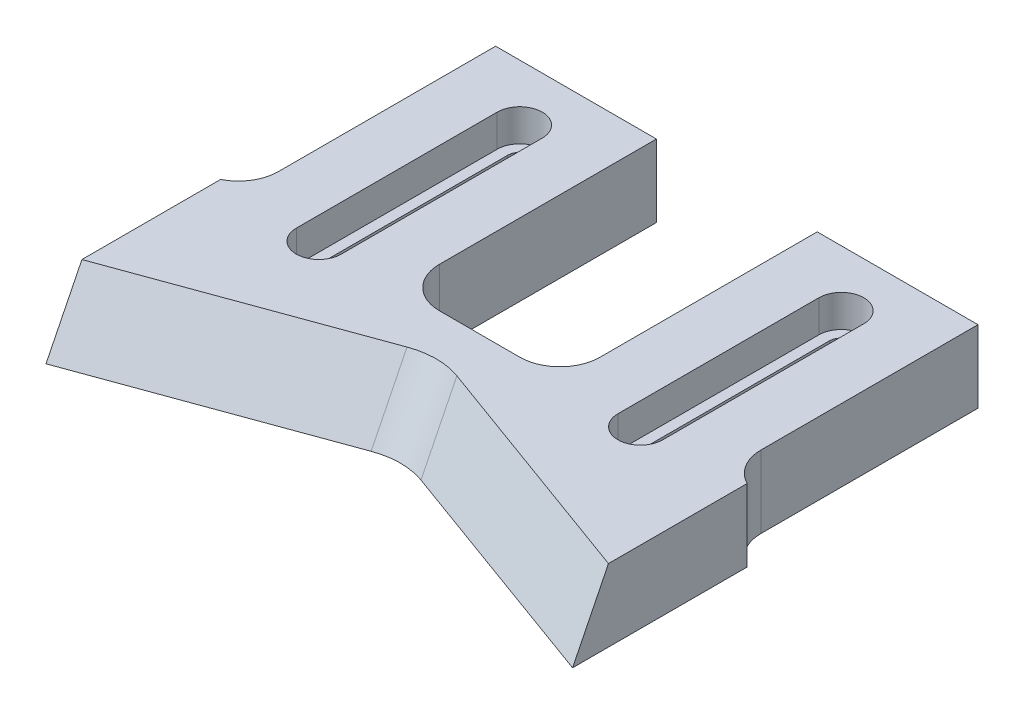
SolidWorks part; units mm, degrees
material "POM Acetal Copolymer"
ref_plane "Front Plane" through (0, 0, 0) normal (0, 0, 1) x (1, 0, 0)
ref_plane "Top Plane" through (0, 0, 0) normal (0, 1, 0) x (1, 0, 0)
ref_plane "Right Plane" through (0, 0, 0) normal (1, 0, 0) x (0, 0, -1)
sketch "Sketch1" plane through (0, 0, 0) normal (0, 1, 0) x (1, 0, 0)
  line L0 (0, 0) -> (0, 55)
  line L1 (0, 55) -> (75.5, 55)
  line L2 (75.5, 55) -> (75.5, 0)
  line L3 (75.5, 0) -> (37.75, 13.7399)
  line L4 (37.75, 13.7399) -> (0, 0)
  dimension "D1" = 55
  dimension "D2" = 70
  dimension "D3" = 75.5
extrude "Boss-Extrude1" add sketch "Sketch1" along normal blind 9
sketch "Sketch4" plane through (0, 9, 0) normal (0, 1, 0) x (1, 0, 0)
  line L0 (17.75, 48) -> (17.75, 23) construction
  line L1 (19.25, 48) -> (19.25, 23)
  line L2 (16.25, 48) -> (16.25, 23)
  line L3 (57.75, 48) -> (57.75, 23) construction
  line L4 (59.25, 48) -> (59.25, 23)
  line L5 (56.25, 48) -> (56.25, 23)
  line L6 (75.5, 55) -> (0, 55) construction
  line L9 (75.5, 55) -> (0, 55) construction
  arc A0 (19.25, 48) -> (16.25, 48) centre (17.75, 48) ccw
  arc A1 (16.25, 23) -> (19.25, 23) centre (17.75, 23) ccw
  arc A2 (59.25, 48) -> (56.25, 48) centre (57.75, 48) ccw
  arc A3 (56.25, 23) -> (59.25, 23) centre (57.75, 23) ccw
  point P2 (17.75, 35.5)
  point P7 (57.75, 35.5)
  point P14 (37.75, 55)
  dimension "D1" = 3
  dimension "D2" = 3
  dimension "D3" = 40
  dimension "D4" = 20
  dimension "D5" = 25
  dimension "D6" = 7
extrude "Cut-Extrude2" cut sketch "Sketch4" against normal up to next
sketch "Sketch5" plane through (0, 9, 0) normal (0, 1, 0) x (1, 0, 0)
  line L0 (75.5, 55) -> (0, 55) construction
  line L1 (27.75, 55) -> (47.75, 55)
  line L2 (27.75, 55) -> (27.75, 23)
  line L3 (27.75, 23) -> (47.75, 23)
  line L4 (47.75, 55) -> (47.75, 23)
  line L7 (67.75, 55) -> (75.5, 55)
  line L8 (0, 55) -> (7.75, 55)
  line L9 (0, 55) -> (0, 23)
  line L10 (0, 23) -> (7.75, 23)
  line L11 (7.75, 55) -> (7.75, 23)
  line L12 (67.75, 55) -> (67.75, 23)
  line L13 (67.75, 23) -> (75.5, 23)
  line L14 (75.5, 55) -> (75.5, 23)
  arc A0 (19.25, 48) -> (16.25, 48) centre (17.75, 48) ccw construction
  arc A1 (59.25, 48) -> (56.25, 48) centre (57.75, 48) ccw construction
  point P6 (17.75, 49.5)
  point P21 (57.75, 49.5)
  dimension "D1" = 20
  dimension "D2" = 20
  dimension "D3" = 32
  dimension "D4" = 10
  dimension "D5" = 10
extrude "Cut-Extrude3" cut sketch "Sketch5" against normal blind 10
fillet "Fillet1" radius 5 4 edges at (67.75, 4.5, -23) (47.75, 4.5, -23) (27.75, 4.5, -23) (7.75, 4.5, -23)
sketch "Sketch6" plane through (0, 9, 0) normal (0, 1, 0) x (1, 0, 0)
  line L0 (17.75, 48) -> (17.75, 23) construction
  line L1 (20.55, 48) -> (20.55, 23)
  line L2 (14.95, 48) -> (14.95, 23)
  line L3 (57.75, 48) -> (57.75, 23) construction
  line L4 (60.55, 48) -> (60.55, 23)
  line L5 (54.95, 48) -> (54.95, 23)
  arc A0 (20.55, 48) -> (14.95, 48) centre (17.75, 48) ccw
  arc A1 (14.95, 23) -> (20.55, 23) centre (17.75, 23) ccw
  arc A2 (60.55, 48) -> (54.95, 48) centre (57.75, 48) ccw
  arc A3 (54.95, 23) -> (60.55, 23) centre (57.75, 23) ccw
  point P4 (17.75, 35.5)
  point P9 (57.75, 35.5)
  dimension "D1" = 5.6
  dimension "D2" = 5.6
extrude "Cut-Extrude4" cut sketch "Sketch6" against normal blind 4
chamfer "Chamfer1" distance 9 angle 25 2 edges at (56.625, 9, -6.8699) (18.875, 9, -6.8699) first distance on face at (56.625, 4.5, -6.8699) first distance on face at (18.875, 4.5, -6.8699)
fillet "Fillet2" radius 10 1 edges at (37.75, 4.5, -15.9729)
sketch "Sketch7" plane through (0, 9, 0) normal (0, 1, 0) x (1, 0, 0)
  line L1 (0, 0) -> (5, 0)
  line L2 (0, 0) -> (0, 33.0851)
  line L3 (0, 33.0851) -> (5, 33.0851)
  line L4 (5, 0) -> (5, 33.0851)
  line L5 (75.5, 0) -> (70.5, 0)
  line L6 (75.5, 0) -> (75.5, 33.7453)
  line L7 (75.5, 33.7453) -> (70.5, 33.7453)
  line L8 (70.5, 0) -> (70.5, 33.7453)
  dimension "D1" = 5
extrude "Cut-Extrude5" cut sketch "Sketch7" against normal up to next
